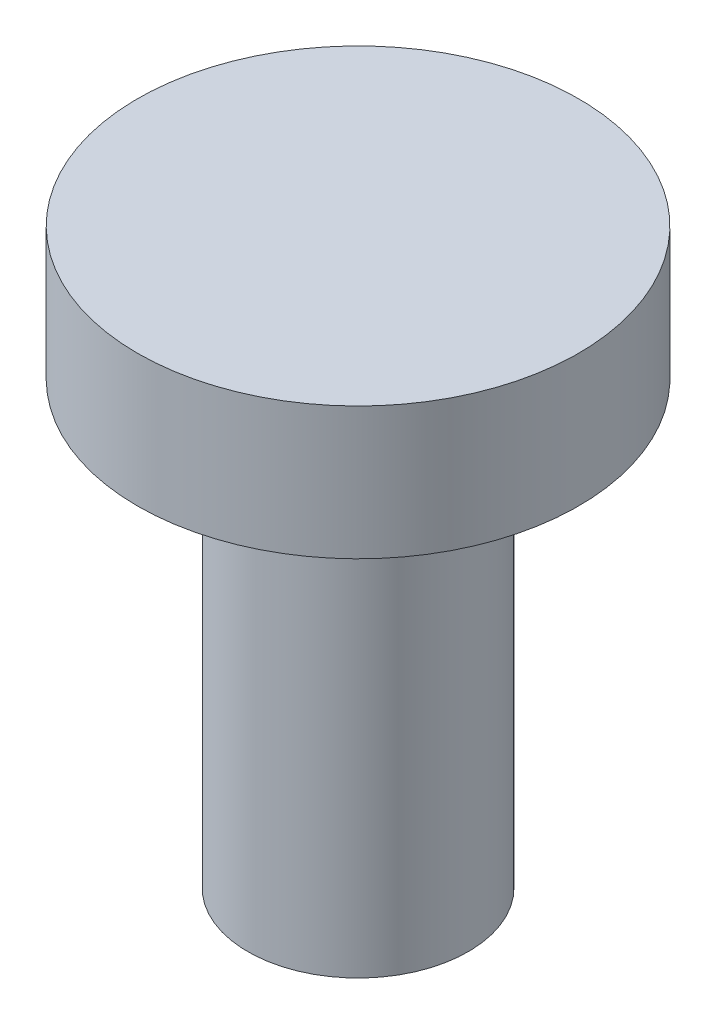
SolidWorks part; units mm, degrees
ref_plane "Front Plane" through (0, 0, 0) normal (0, 0, 1) x (1, 0, 0)
ref_plane "Top Plane" through (0, 0, 0) normal (0, 1, 0) x (1, 0, 0)
ref_plane "Right Plane" through (0, 0, 0) normal (1, 0, 0) x (0, 0, -1)
sketch "Sketch1" plane through (0, 0, 0) normal (0, 1, 0) x (1, 0, 0)
  circle A0 centre (0, 0) radius 5
  dimension "D1" = 10
extrude "Boss-Extrude1" add sketch "Sketch1" along normal blind 3
sketch "Sketch2" plane through (0, 0, 0) normal (0, -1, 0) x (1, 0, 0)
  circle A0 centre (0, 0) radius 2.5
  dimension "D1" = 5
extrude "Boss-Extrude2" add sketch "Sketch2" along normal blind 10
